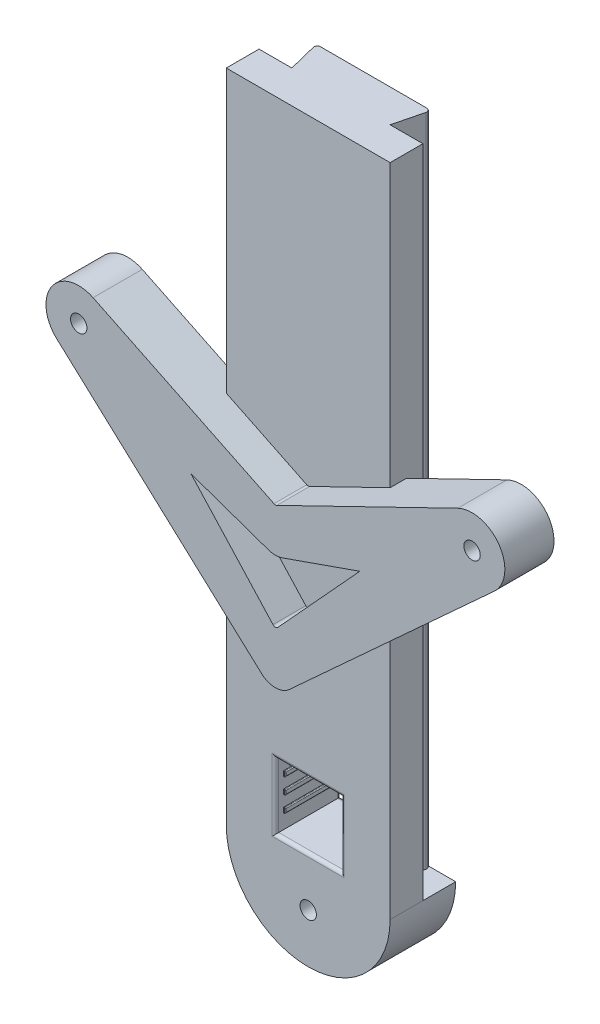
SolidWorks part; units mm, degrees
ref_plane "前视基准面" through (0, 0, 0) normal (0, 0, 1) x (1, 0, 0)
ref_plane "上视基准面" through (0, 0, 0) normal (0, 1, 0) x (1, 0, 0)
ref_plane "右视基准面" through (0, 0, 0) normal (1, 0, 0) x (0, 0, -1)
other "Configuration Table"
sketch "草图1" plane through (0, 0, 0) normal (0, 1, 0) x (1, 0, 0)
  line L0 (0, -116.5119) -> (0, 5709.082) construction
  line L1 (-3, 0) -> (3, 0)
  line L2 (3, 0) -> (3.5, 2)
  line L3 (3.5, 2) -> (-3.5, 2)
  line L4 (0, 2) -> (0, 0)
  line L5 (-3, 0) -> (-3.5, 2)
  line L6 (3, 0) -> (5, 0)
  line L7 (5, 0) -> (5, -2)
  line L8 (5, -2) -> (-5, -2)
  line L9 (-3, 0) -> (-5, 0)
  line L10 (-5, 0) -> (-5, -2)
  point P13 (0, -2)
  dimension "D1" = 3
  dimension "D2" = 3.5
  dimension "D3" = 2
  dimension "D4" = 2
  dimension "D5" = 2
extrude "凸台-拉伸1" add sketch "草图1" along normal blind 40 contours L5 L1 L4 L3 | L3 L4 L1 L2 | L0 L8 L7 L6 L1 | L8 L0 L1 L9 L10 region at (1.6282, 0, -1.0256) region at (-1.6282, 0, -1.0256) region at (2.5, 0, 1) region at (-2.5, 0, 1)
fillet "圆角1" radius 0.2 2 edges at (3.5, 20, -2) (-3.5, 20, -2)
sketch "草图2" plane through (0, 0, 2) normal (0, 0, 1) x (1, 0, 0)
  line L0 (-5, 0) -> (5, 0)
  arc A0 (-5, 0) -> (5, 0) centre (0, 0) ccw
extrude "凸台-拉伸2" add sketch "草图2" against normal blind 4
sketch "草图3" plane through (0, 0, 2) normal (0, 0, 1) x (1, 0, 0)
  line L1 (-2, 1) -> (2, 1)
  line L6 (2, 1) -> (2, 5)
  line L7 (2, 5) -> (-2, 5)
  line L8 (-2, 1) -> (-2, 5)
  circle A0 centre (0, -2) radius 0.5
  point P11 (0, 5)
  point P13 (0, 5)
  dimension "D2" = 1
  dimension "D4" = 4
  dimension "D5" = 2
extrude "切除-拉伸1" cut sketch "草图3" against normal blind 4
fillet "圆角2" radius 0.2 8 edges at (0, 1, -2) (2, 3, -2) (0, 5, -2) (-2, 3, -2) (-2, 3, 2) (0, 5, 2) (0, 1, 2) (2, 3, 2)
sketch "草图4" plane through (-2, 0, 0) normal (1, 0, 0) x (0, 0, -1)
  line L0 (1.8, 3) -> (-1.8, 3) construction
  line L1 (1.8, 1) -> (1.8, 5) construction
  line L2 (-1.8, 5) -> (-1.8, 1) construction
  line L3 (0, -996.85) -> (0, 49003.15) construction
  line L4 (-1.5, 3.15) -> (1.5, 3.15)
  line L5 (-1.5, 3.15) -> (-1.5, 2.85)
  line L6 (-1.5, 2.85) -> (1.5, 2.85)
  line L7 (1.5, 3.15) -> (1.5, 2.85)
  line L8 (-1.5, 3.15) -> (1.5, 2.85) construction
  line L9 (-1.5, 2.85) -> (1.5, 3.15) construction
  line L10 (-1.5, 2.1858) -> (1.5, 2.1858)
  line L11 (-1.5, 4.1142) -> (1.5, 4.1142)
  line L12 (-1.5, 4.1142) -> (-1.5, 3.8142)
  line L13 (-1.5, 3.8142) -> (1.5, 3.8142)
  line L14 (1.5, 4.1142) -> (1.5, 3.8142)
  line L15 (-1.5, 4.1142) -> (1.5, 3.8142) construction
  line L16 (-1.5, 3.8142) -> (1.5, 4.1142) construction
  line L17 (1.5, 1.8858) -> (1.5, 2.1858)
  line L18 (-1.5, 1.8858) -> (1.5, 1.8858)
  line L19 (-1.5, 1.8858) -> (-1.5, 2.1858)
  point P6 (0, 3)
  point P12 (0, 3.9642)
  point P14 (0, 3.15)
  dimension "D1" = 0.3
  dimension "D2" = 3
  dimension "D3" = 0.3
  dimension "D4" = 3
extrude "凸台-拉伸3" add sketch "草图4" along normal blind 0.1
fillet "圆角3" radius 0.05 12 edges at (-1.9, 2.0358, 1.5) (-1.9, 1.8858, 0) (-1.9, 2.0358, -1.5) (-1.9, 2.1858, 0) (-1.9, 3, 1.5) (-1.9, 2.85, 0) (-1.9, 3.15, 0) (-1.9, 3, -1.5) (-1.9, 3.9642, 1.5) (-1.9, 4.1142, 0) (-1.9, 3.8142, 0) (-1.9, 3.9642, -1.5)
mirror "镜向1" about plane through (0, 0, 0) normal (1, 0, 0) of "圆角3", "凸台-拉伸3"
sketch "草图7" plane through (0, 0, 2) normal (0, 0, 1) x (1, 0, 0)
  line L0 (0, -960) -> (0, 10.75) construction
  line L1 (5, 40) -> (-5, 40) construction
  line L2 (0, 40) -> (0, 24)
  line L3 (-1000, 24) -> (7.4257, 24) construction
  line L4 (0, 24) -> (7.4257, 24)
  line L5 (0, 24) -> (0, 20.3899)
  line L6 (0, 17.75) -> (0, 13.8514)
  line L7 (0, 20.3899) -> (11.1255, 25.7987)
  line L8 (0.4134, 17.8203) -> (5.1528, 19.4812)
  line L9 (0, 13.8514) -> (5.1528, 19.4812)
  line L10 (13.3503, 22.5247) -> (0.844, 11.0779)
  line L11 (0, 13.8514) -> (0, 17.75) construction
  line L12 (12, 24) -> (49000, 24) construction
  line L13 (0, 20.3899) -> (0, 49040) construction
  line L14 (0, 20.3899) -> (-11.1255, 25.7987)
  line L15 (-13.3503, 22.5247) -> (-0.844, 11.0779)
  line L16 (0, 13.8514) -> (-5.1528, 19.4812)
  line L17 (-0.4134, 17.8203) -> (-5.1528, 19.4812)
  arc A0 (13.3503, 22.5247) -> (11.1255, 25.7987) centre (12, 24) ccw
  arc A1 (-0.4134, 17.8203) -> (0.4134, 17.8203) centre (0, 19) ccw
  arc A2 (-0.844, 11.0779) -> (0.844, 11.0779) centre (0, 12) ccw
  arc A3 (-13.3503, 22.5247) -> (-11.1255, 25.7987) centre (-12, 24) cw
  arc A4 (0.844, 11.0779) -> (-0.844, 11.0779) centre (0, 12) cw
  arc A5 (0.4134, 17.8203) -> (-0.4134, 17.8203) centre (0, 19) cw
  circle A6 centre (-12, 24) radius 0.5
  circle A7 centre (12, 24) radius 0.5
  point P5 (0, 40)
  line M17 (-5, 40) -> (-5, 0)
  line M19 (5, 0) -> (5, 40)
  dimension "D3" = 4
  dimension "D5" = 2.5
  dimension "D7" = 2.5
  dimension "D8" = 1
  dimension "D9" = 1
  dimension "D1" = 16
  dimension "D2" = 12
  dimension "D4" = 5
  dimension "D6" = 7
extrude "凸台-拉伸4" add sketch "草图7" along normal mid plane 2 contours L15 A2 L10 L9 L16 M19 M17 | L17 A1 L8 L7 L14 M19 M17 | A3 L15 L16 L17 L14 M17 | L10 A0 L7 L8 L9 M19 region at (0, 20.1188, 2) region at (8.7649, 21.424, 2) region at (-8.7649, 21.424, 2) region at (4.8683, 17.098, 2)
extrude "凸台-拉伸5" add sketch "草图7<3>" along normal blind 2 contours L10 A0 L7 L8 L9 M19 | L17 A1 L8 L7 L14 M19 M17 | L15 A2 L10 L9 L16 M19 M17 | A3 L15 L16 L17 L14 M17 region at (0, 20.1188, 2) region at (8.7649, 21.424, 2) region at (-8.7649, 21.424, 2) region at (4.8683, 17.098, 2)
sketch "草图7<3>" plane through (0, 0, 2) normal (0, 0, 1) x (1, 0, 0) same geometry as "草图7"
fillet "圆角4" radius 0.2 2 edges at (0, 20.3899, 3) (0, 13.8514, 3)
